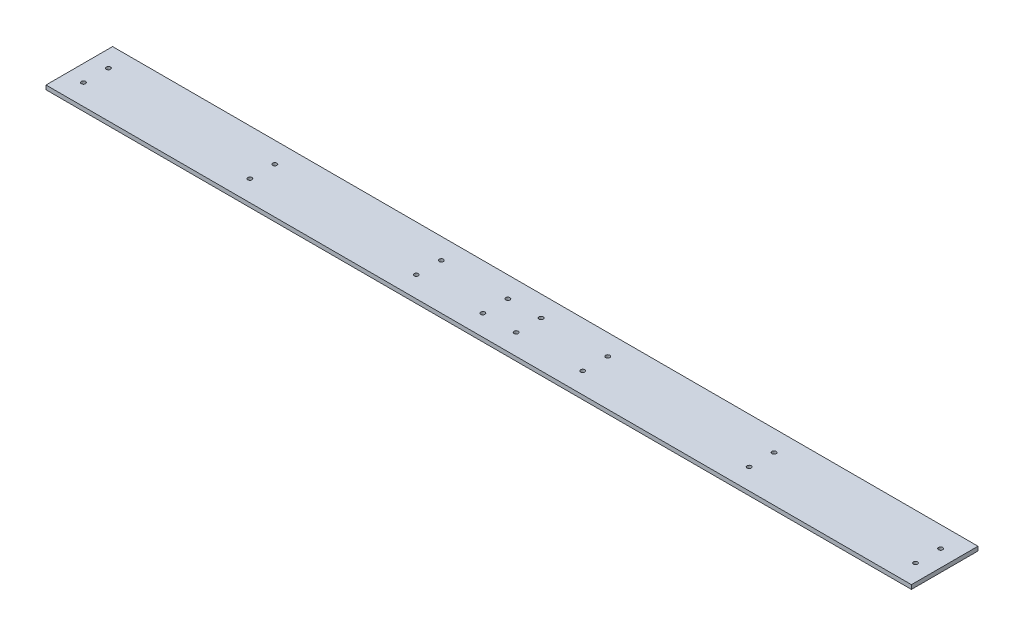
SolidWorks part; units mm, degrees
ref_plane "Front Plane" through (0, 0, 0) normal (0, 0, 1) x (1, 0, 0)
ref_plane "Top Plane" through (0, 0, 0) normal (0, 1, 0) x (1, 0, 0)
ref_plane "Right Plane" through (0, 0, 0) normal (1, 0, 0) x (0, 0, -1)
sketch "Sketch1" plane through (0, 0, 0) normal (0, 1, 0) x (1, 0, 0)
  line L0 (0, 15) -> (0, -15) construction
  line L1 (-20, 40) -> (-20, -40)
  line L2 (-20, -40) -> (1020, -40)
  line L3 (1020, -40) -> (1020, 40)
  line L4 (1020, 40) -> (-20, 40)
  line L5 (-20, 0) -> (0, 0) construction
  line L6 (0, 0) -> (1020, 0) construction
  line L7 (-78.9282, 15) -> (-78.9282, -15) construction
  line L8 (0, -15) -> (200, -15) construction
  line L9 (-78.9282, 15) -> (0, 15) construction
  line L10 (1058.1654, 5) -> (1058.1654, -25) construction
  line L11 (500, 40) -> (500, -40) construction
  line L12 (400, 15) -> (480, 15) construction
  line L13 (480, 15) -> (520, 15) construction
  line L14 (480, 15) -> (480, -15) construction
  line L15 (480, -15) -> (520, -15) construction
  line L16 (520, 15) -> (520, -15) construction
  line L17 (480, 15) -> (520, -15) construction
  line L18 (480, -15) -> (520, 15) construction
  circle A0 centre (0, 15) radius 2.5
  circle A1 centre (0, -15) radius 2.5
  circle A2 centre (200, -15) radius 2.5
  circle A3 centre (200, 15) radius 2.5
  circle A4 centre (400, -15) radius 2.5
  circle A5 centre (400, 15) radius 2.5
  circle A6 centre (600, -15) radius 2.5
  circle A7 centre (600, 15) radius 2.5
  circle A8 centre (800, -15) radius 2.5
  circle A9 centre (800, 15) radius 2.5
  circle A10 centre (1058.1654, 5) radius 2.5 construction
  circle A11 centre (1058.1654, -25) radius 2.5 construction
  circle A12 centre (-78.9282, -15) radius 2.5 construction
  circle A13 centre (-78.9282, 15) radius 2.5 construction
  circle A14 centre (1000, -15) radius 2.5
  circle A15 centre (1000, 15) radius 2.5
  circle A16 centre (480, 15) radius 2.5
  circle A17 centre (520, 15) radius 2.5
  circle A18 centre (520, -15) radius 2.5
  circle A19 centre (480, -15) radius 2.5
  point P39 (500, 0)
  dimension "D2" = 5
  dimension "D9" = 80
  dimension "D1" = 30
  dimension "D3" = 20
  dimension "D4" = 20
  dimension "D5" = 6
  dimension "D6" = 200
  dimension "D7" = 40
extrude "Boss-Extrude1" add sketch "Sketch1" along normal blind 5
equation "\"skin_sheetmetal_thickness\"= 0.80"
equation "\"base_width_skin_spacer\" = 50"
equation "\"base_width_skin_inner\" = \"base_width_skin_spacer\" + 2 * \"skin_sheetmetal_thickness\""
equation "\"base_width_skin_outer\" = \"base_width_skin_inner\" + 2 * \"skin_sheetmetal_thickness\""
equation "\"bend_cut_width\"= 3"
equation "\"bend_cut_length\"= 3"
equation "\"bend_offset_inner\"= 12.5"
equation "\"bend_offset_outer\" = \"bend_offset_inner\" + \"skin_sheetmetal_thickness\""
equation "\"border_offset_ends\"= 20"
equation "\"border_offset_sides\"= 10"
equation "\"border_offset_flange_horiz\"= 10"
equation "\"rivet_size\"= 4.3"
equation "\"rivet_offset_ends\"= 80"
equation "\"rivet_spacing_horiz\"= 200"
equation "\"rivet_spacing_vert\"= 30"
equation "\"rivet_spacing_offset_right\"= 40"
equation "\"base_length\"= 200"
